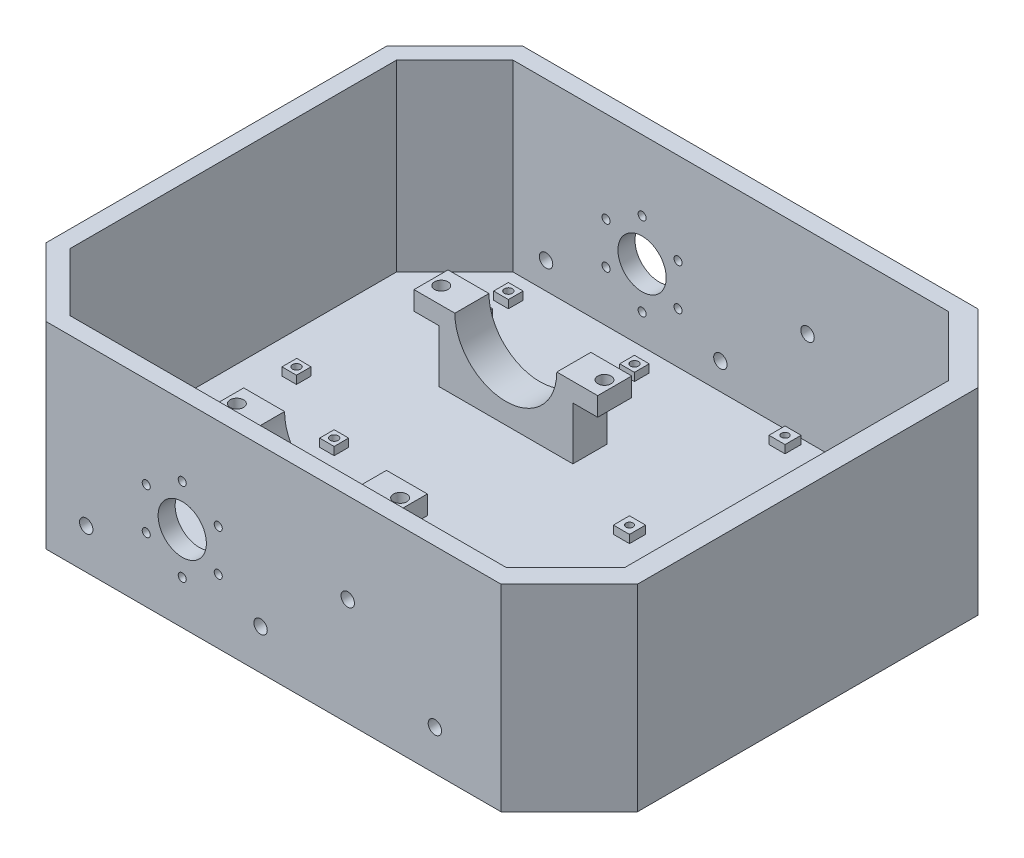
SolidWorks part; units mm, degrees
ref_plane "Front Plane" through (0, 0, 0) normal (0, 0, 1) x (1, 0, 0)
ref_plane "Top Plane" through (0, 0, 0) normal (0, 1, 0) x (1, 0, 0)
ref_plane "Right Plane" through (0, 0, 0) normal (1, 0, 0) x (0, 0, -1)
sketch "Sketch2" plane through (0, 0, 0) normal (0, 1, 0) x (1, 0, 0)
  line L1 (-127, 76.2) -> (63.5, 76.2)
  line L2 (-127, 76.2) -> (-127, -101.6)
  line L3 (-127, -101.6) -> (63.5, -101.6)
  line L4 (63.5, 76.2) -> (63.5, -101.6)
  dimension "D1" = 190.5
  dimension "D2" = 177.8
  dimension "D3" = 76.2
  dimension "D4" = 63.5
extrude "Boss-Extrude1" add sketch "Sketch2" along normal blind 5.08
chamfer "Chamfer1" distance 25.4 angle 45 2 edges at (-127, 2.54, -76.2) (-127, 2.54, 101.6)
sketch "Sketch4" plane through (0, 5.08, 0) normal (0, 1, 0) x (1, 0, 0)
  line L0 (57.15, 69.85) -> (-98.9697, 69.85)
  line L1 (-98.9697, 69.85) -> (-120.65, 48.1697)
  line L2 (-120.65, 48.1697) -> (-120.65, -73.5697)
  line L3 (-120.65, -73.5697) -> (-98.9697, -95.25)
  line L4 (-98.9697, -95.25) -> (57.15, -95.25)
  line L6 (63.5, 76.2) -> (-101.6, 76.2)
  line L7 (-101.6, 76.2) -> (-127, 50.8)
  line L8 (-127, 50.8) -> (-127, -76.2)
  line L9 (-127, -76.2) -> (-101.6, -101.6)
  line L10 (-101.6, -101.6) -> (63.5, -101.6)
  line L11 (63.5, -101.6) -> (63.5, 76.2)
  line L12 (63.5, 76.2) -> (-101.6, 76.2)
  line L13 (-101.6, 76.2) -> (-127, 50.8)
  line L14 (-127, 50.8) -> (-127, -76.2)
  line L15 (-127, -76.2) -> (-101.6, -101.6)
  line L16 (-101.6, -101.6) -> (63.5, -101.6)
  line L17 (63.5, -101.6) -> (63.5, -95.25)
  line L18 (57.15, 69.85) -> (63.5, 69.85)
  line L19 (57.15, -95.25) -> (63.5, -95.25)
  line L20 (63.5, 69.85) -> (63.5, 76.2)
  line L21 (63.5, -101.6) -> (63.5, 76.2) construction
  line L22 (57.15, -95.25) -> (57.15, 69.85) construction
  dimension "D2" = 6.35
  dimension "D1" = 0
extrude "Boss-Extrude3" add sketch "Sketch4" along normal blind 68.42
sketch "Sketch5" plane through (0, 0, 101.6) normal (0, 0, 1) x (1, 0, 0)
  line L0 (-150.3871, 38.1) -> (157.7429, 38.1) construction
  line L1 (-101.6, 0) -> (63.5, 0) construction
  line L2 (0, -14.9262) -> (0, 83.7522) construction
  line L3 (-50.8, 49.8289) -> (-50.8, 11.4994) construction
  line L5 (-71.0506, 31.75) -> (-33.7726, 31.75) construction
  circle A0 centre (-50.8, 31.75) radius 9
  circle A1 centre (-50.8, 31.75) radius 15.5 construction
  circle A2 centre (-50.8, 47.25) radius 1.5
  circle A3 centre (-37.3766, 39.5) radius 1.5
  circle A4 centre (-37.3766, 24) radius 1.5
  circle A5 centre (-50.8, 16.25) radius 1.5
  circle A6 centre (-64.2234, 24) radius 1.5
  circle A7 centre (-64.2234, 39.5) radius 1.5
  dimension "D2" = 18
  dimension "D5" = 31
  dimension "D6" = 3
  dimension "D1" = 38.1
  dimension "D3" = 50.8
  dimension "D4" = 6.35
  dimension "D7" = 6
extrude "Cut-Extrude1" cut sketch "Sketch5" against normal through all
sketch "Sketch10" plane through (63.5, 0, 0) normal (1, 0, 0) x (0, 0, -1)
  line L1 (-101.6, 0) -> (76.2, 0)
  line L2 (-101.6, 0) -> (-101.6, 73.5)
  line L3 (-101.6, 73.5) -> (76.2, 73.5)
  line L4 (76.2, 0) -> (76.2, 73.5)
extrude "Boss-Extrude6" add sketch "Sketch10" along normal blind 30
chamfer "Chamfer3" distance 25.4 angle 45 2 edges at (93.5, 36.75, -76.2) (93.5, 36.75, 101.6)
sketch "Sketch11" plane through (0, 73.5, 0) normal (0, 1, 0) x (1, 0, 0)
  line L0 (63.5, -95.25) -> (85.7572, -72.9928)
  line L1 (85.7572, -72.9928) -> (85.7572, 47.5928)
  line L2 (85.7572, 47.5928) -> (63.5, 69.85)
  line L4 (63.5, -95.25) -> (63.5, 69.85)
  line L5 (85.7572, 47.5928) -> (62.625, 70.725) construction
  line L6 (62.625, -96.125) -> (85.7572, -72.9928) construction
  line L8 (93.5, -76.2) -> (93.5, 50.8)
  line L9 (93.5, 50.8) -> (68.1, 76.2)
  line L10 (68.1, 76.2) -> (-101.6, 76.2)
  line L11 (-101.6, 76.2) -> (-127, 50.8)
  line L12 (-127, 50.8) -> (-127, -76.2)
  line L13 (-127, -76.2) -> (-101.6, -101.6)
  line L14 (-101.6, -101.6) -> (68.1, -101.6)
  line L15 (68.1, -101.6) -> (93.5, -76.2)
  line L16 (93.5, -76.2) -> (93.5, 50.8)
  line L17 (93.5, 50.8) -> (68.1, 76.2)
  line L23 (68.1, -101.6) -> (93.5, -76.2)
  line M22 (63.5, 69.85) -> (63.5, -95.25)
  dimension "D1" = 0
extrude "Cut-Extrude2" cut sketch "Sketch11" along direction (0, 1, 0) on the side against the normal up to surface (68.42 mm away) contours L1 L2 L0 M22 region at (74.0506, 73.5, 12.7) up to face at (-52.0399, 5.08, 12.7)
sketch "Sketch12" plane through (0, 0, 95.25) normal (0, 0, -1) x (-1, 0, 0)
  line L1 (-63.5, 5.08) -> (98.9697, 5.08) construction
  line L2 (25.8, 5.08) -> (75.8, 5.08)
  line L3 (25.8, 5.08) -> (25.8, 31.75)
  line L4 (25.8, 31.75) -> (31.8, 31.75)
  line L5 (75.8, 5.08) -> (75.8, 31.75)
  line L6 (69.8, 31.75) -> (75.8, 31.75)
  arc A0 (31.8, 31.75) -> (69.8, 31.75) centre (50.8, 31.75) ccw
  dimension "D1" = 38
  dimension "D2" = 25
  dimension "D3" = 25
extrude "Boss-Extrude7" add sketch "Sketch12" along normal blind 12.7 from offset 38.1
ref_plane "Plane1" through (0, 0, 12.7) normal (0, 0, 1) x (1, 0, 0)
sketch "Sketch13" plane through (0, 31.75, 0) normal (0, 1, 0) x (1, 0, 0)
  line L0 (-25.8, -44.45) -> (-75.8, -44.45) construction
  line L1 (-31.8, -44.45) -> (-16.56, -44.45)
  line L2 (-31.8, -44.45) -> (-31.8, -57.15)
  line L3 (-31.8, -57.15) -> (-16.56, -57.15)
  line L4 (-16.56, -44.45) -> (-16.56, -57.15)
  line L5 (-31.8, -44.45) -> (-25.8, -44.45) construction
  line L6 (-31.8, -57.15) -> (-25.8, -57.15) construction
  line L7 (-31.8, -44.45) -> (-31.8, -57.15) construction
  dimension "D1" = 15.24
extrude "Boss-Extrude8" add sketch "Sketch13" against normal blind 7
sketch "Sketch14" plane through (0, 31.75, 0) normal (0, 1, 0) x (1, 0, 0)
  line L0 (-31.8, -44.45) -> (-16.56, -44.45) construction
  line L2 (-20.37, -50.8) -> (-20.37, -44.45) construction
  line L3 (-20.37, -50.8) -> (-20.37, -57.15) construction
  line L4 (-31.8, -57.15) -> (-16.56, -57.15) construction
  line L5 (-31.8, -44.45) -> (-31.8, -57.15) construction
  circle A0 centre (-20.37, -50.8) radius 2.5
  dimension "D1" = 5
  dimension "D2" = 11.43
extrude "Cut-Extrude3" cut sketch "Sketch14" against normal blind 10
ref_plane "Plane2" through (-50.8, 0, 0) normal (-1, 0, 0) x (0, 0, 1)
mirror "Mirror2" about plane through (-50.8, 0, 0) normal (-1, 0, 0) of "Boss-Extrude8"
mirror "Mirror3" about plane through (-50.8, 0, 0) normal (-1, 0, 0) of "Cut-Extrude3"
mirror "Mirror4" about plane through (0, 0, 12.7) normal (0, 0, 1) of "Boss-Extrude7", "Boss-Extrude8", "Cut-Extrude3", "Mirror3", "Mirror2"
sketch "Sketch15" plane through (0, 0, 101.6) normal (0, 0, 1) x (1, 0, 0)
  line L0 (-101.6, 0) -> (68.1, 0) construction
  line L1 (-101.6, 73.5) -> (-101.6, 0) construction
  circle A0 centre (-86.6, 15) radius 2.5
  circle A1 centre (-21.6, 15) radius 2.5
  circle A2 centre (43.4, 15) radius 2.5
  circle A3 centre (10.9, 40) radius 2.5
  dimension "D1" = 5
  dimension "D2" = 40
  dimension "D4" = 65
  dimension "D5" = 15
  dimension "D6" = 15
  dimension "D3" = 130
  dimension "D7" = 32.5
extrude "Cut-Extrude4" cut sketch "Sketch15" against normal through all contours A1 | A3 | A2 | A0 region at (-21.6, 15, 101.6) region at (43.4, 15, 101.6) region at (10.9, 40, 101.6)
sketch "Sketch17" plane through (0, 5.08, 0) normal (0, 1, 0) x (1, 0, 0)
  line L0 (-98.9697, 69.85) -> (63.5, 69.85) construction
  line L1 (4.5, 67.85) -> (10.5, 67.85)
  line L2 (4.5, 67.85) -> (4.5, 61.85)
  line L3 (4.5, 61.85) -> (10.5, 61.85)
  line L4 (10.5, 67.85) -> (10.5, 61.85)
  line L5 (4.5, 67.85) -> (10.5, 61.85) construction
  line L6 (4.5, 61.85) -> (10.5, 67.85) construction
  line L7 (59.5, 61.85) -> (53.5, 61.85)
  line L8 (59.5, 61.85) -> (59.5, 67.85)
  line L9 (59.5, 67.85) -> (53.5, 67.85)
  line L10 (53.5, 61.85) -> (53.5, 67.85)
  line L11 (59.5, 61.85) -> (53.5, 67.85) construction
  line L12 (59.5, 67.85) -> (53.5, 61.85) construction
  line L13 (4.5, 9.85) -> (10.5, 9.85)
  line L14 (4.5, 9.85) -> (4.5, 3.85)
  line L15 (4.5, 3.85) -> (10.5, 3.85)
  line L16 (10.5, 9.85) -> (10.5, 3.85)
  line L17 (4.5, 9.85) -> (10.5, 3.85) construction
  line L18 (4.5, 3.85) -> (10.5, 9.85) construction
  line L19 (53.5, 9.85) -> (59.5, 9.85)
  line L20 (53.5, 9.85) -> (53.5, 3.85)
  line L21 (53.5, 3.85) -> (59.5, 3.85)
  line L22 (59.5, 9.85) -> (59.5, 3.85)
  line L23 (53.5, 9.85) -> (59.5, 3.85) construction
  line L24 (53.5, 3.85) -> (59.5, 9.85) construction
  circle A0 centre (7.5, 64.85) radius 1.35
  circle A1 centre (56.5, 64.85) radius 1.35
  circle A2 centre (7.5, 6.85) radius 1.35
  circle A3 centre (56.5, 6.85) radius 1.35
  dimension "D3" = 2.7
  dimension "D1" = 58
  dimension "D2" = 49
  dimension "D4" = 6
  dimension "D5" = 5
  dimension "D6" = 4
extrude "Boss-Extrude9" add sketch "Sketch17" along normal blind 3
sketch "Sketch18" plane through (0, 5.08, 0) normal (0, 1, 0) x (1, 0, 0)
  line L0 (-120.65, -73.5697) -> (-120.65, 48.1697) construction
  line L1 (-108.3746, -1.34) -> (-102.9743, -1.4388)
  line L2 (-108.3746, -1.34) -> (-108.3746, -6.84)
  line L3 (-108.3746, -6.84) -> (-102.9743, -6.84)
  line L4 (-102.9743, -1.4388) -> (-102.9743, -6.84)
  line L5 (-108.3746, -1.34) -> (-102.9743, -6.84) construction
  line L6 (-108.3746, -6.84) -> (-102.9743, -1.4388) construction
  line L7 (-78.3506, -17.4143) -> (-72.9494, -17.4143)
  line L8 (-78.3506, -17.4143) -> (-78.3506, -22.8155)
  line L9 (-78.3506, -22.8155) -> (-72.9494, -22.8155)
  line L10 (-72.9494, -17.4143) -> (-72.9494, -22.8155)
  line L11 (-78.3506, -17.4143) -> (-72.9494, -22.8155) construction
  line L12 (-78.3506, -22.8155) -> (-72.9494, -17.4143) construction
  line L13 (-98.9697, 69.85) -> (63.5, 69.85) construction
  line L14 (-93.4, 62.6) -> (-87.9, 62.6)
  line L15 (-93.4, 62.6) -> (-93.4, 57.1)
  line L16 (-93.4, 57.1) -> (-87.9, 57.1)
  line L17 (-87.9, 62.6) -> (-87.9, 57.1)
  line L18 (-93.4, 62.6) -> (-87.9, 57.1) construction
  line L19 (-93.4, 57.1) -> (-87.9, 62.6) construction
  line L20 (-46.4, 62.6) -> (-40.9, 62.6)
  line L21 (-46.4, 62.6) -> (-46.4, 57.1)
  line L22 (-46.4, 57.1) -> (-40.9, 57.1)
  line L23 (-40.9, 62.6) -> (-40.9, 57.1)
  line L24 (-46.4, 62.6) -> (-40.9, 57.1) construction
  line L25 (-46.4, 57.1) -> (-40.9, 62.6) construction
  line L26 (-46.4, 51.2) -> (-40.9, 51.2)
  line L27 (-46.4, 51.2) -> (-46.4, 45.7)
  line L28 (-46.4, 45.7) -> (-40.9, 45.7)
  line L29 (-40.9, 51.2) -> (-40.9, 45.7)
  line L30 (-46.4, 51.2) -> (-40.9, 45.7) construction
  line L31 (-46.4, 45.7) -> (-40.9, 51.2) construction
  line L32 (-93.4, 51.2) -> (-87.9, 51.2)
  line L33 (-93.4, 51.2) -> (-93.4, 45.7)
  line L34 (-93.4, 45.7) -> (-87.9, 45.7)
  line L35 (-87.9, 51.2) -> (-87.9, 45.7)
  line L36 (-93.4, 51.2) -> (-87.9, 45.7) construction
  line L37 (-93.4, 45.7) -> (-87.9, 51.2) construction
  line L38 (-120.65, -73.5697) -> (-120.65, 48.1697) construction
  circle A0 centre (-105.65, -4.1149) radius 1.5
  circle A1 centre (-75.65, -20.1149) radius 1.5
  circle A2 centre (-90.65, 59.85) radius 1.5
  circle A3 centre (-90.65, 48.45) radius 1.5
  circle A4 centre (-43.65, 48.45) radius 1.5
  circle A5 centre (-43.65, 59.85) radius 1.5
  point P38 (0, 0)
  point P39 (0, 0)
  point P40 (0, 0)
  point P41 (0, 0)
  dimension "D1" = 3
  dimension "D2" = 3
  dimension "D7" = 3
  dimension "D3" = 5.5
  dimension "D4" = 30
  dimension "D5" = 16
  dimension "D6" = 15
  dimension "D8" = 5.5
  dimension "D9" = 10
  dimension "D10" = 30
  dimension "D11" = 47
  dimension "D12" = 11.4
extrude "Boss-Extrude10" add sketch "Sketch18" along normal blind 3
